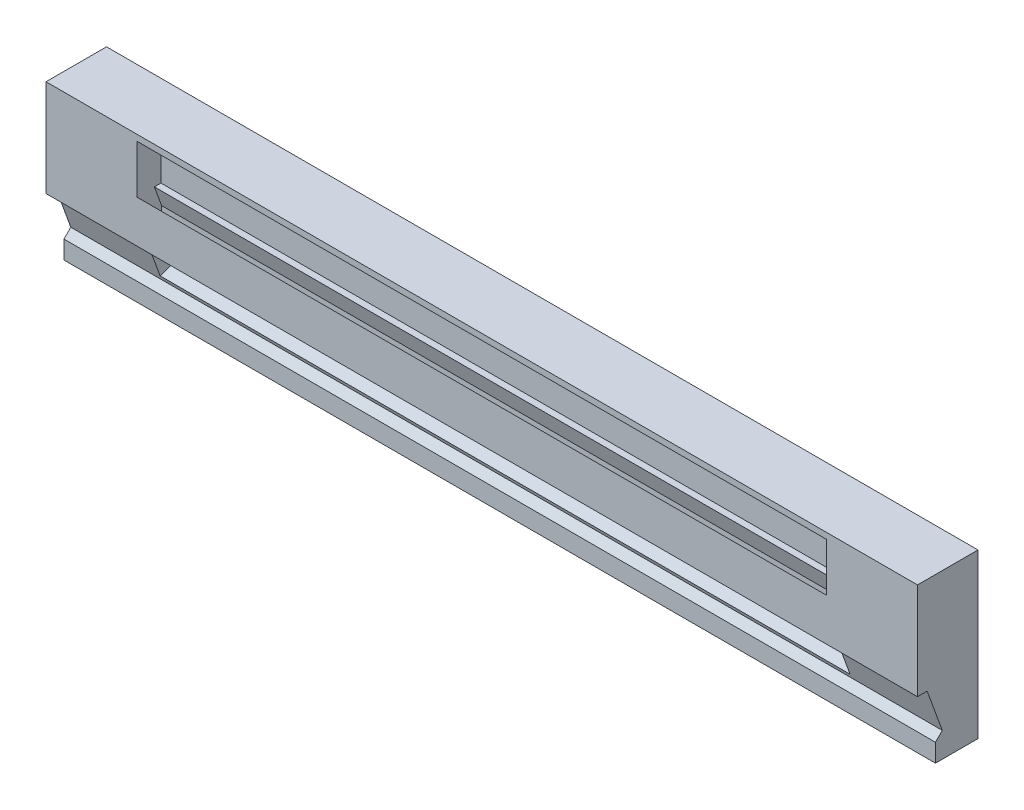
SolidWorks part; units mm, degrees
ref_plane "Front Plane" through (0, 0, 0) normal (0, 0, 1) x (1, 0, 0)
ref_plane "Top Plane" through (0, 0, 0) normal (0, 1, 0) x (1, 0, 0)
ref_plane "Right Plane" through (0, 0, 0) normal (1, 0, 0) x (0, 0, -1)
sketch "Sketch1" plane through (0, 0, 0) normal (1, 0, 0) x (0, 0, -1)
  line L0 (0, 0) -> (44.6494, 0)
  line L1 (44.6494, 0) -> (44.6494, 171.45)
  line L2 (44.6494, 171.45) -> (-18.8506, 171.45)
  line L3 (-18.8506, 171.45) -> (-18.8506, 69.85)
  line L4 (-18.8506, 69.85) -> (-8.6906, 69.85)
  line L5 (-8.6906, 69.85) -> (7.1842, 26.2342)
  line L6 (7.1842, 26.2342) -> (0, 19.05)
  line L7 (0, 19.05) -> (0, 0)
  dimension "D1" = 171.45
  dimension "D2" = 63.5
  dimension "D3" = 101.6
  dimension "D4" = 19.05
  dimension "D5" = 10.16
  dimension "D6" = 10.16
  dimension "D7" = 135
  dimension "D8" = 115
extrude "Boss-Extrude1" add sketch "Sketch1" along normal blind 914.4
sketch "Sketch2" plane through (0, 0, 18.8506) normal (0, 0, 1) x (1, 0, 0)
  line L0 (0, 171.45) -> (0, 69.85) construction
  line L1 (95.25, 165.1) -> (819.15, 165.1)
  line L2 (95.25, 165.1) -> (95.25, 114.3)
  line L3 (95.25, 114.3) -> (819.15, 114.3)
  line L4 (819.15, 165.1) -> (819.15, 114.3)
  line L5 (914.4, 171.45) -> (914.4, 69.85) construction
  line L6 (914.4, 171.45) -> (0, 171.45) construction
  dimension "D1" = 95.25
  dimension "D2" = 95.25
  dimension "D3" = 6.35
  dimension "D4" = 50.8
extrude "Cut-Extrude1" cut sketch "Sketch2" along direction (0, -0.9397, -0.342) on the side against the normal blind 76.2
extrude "Cut-Extrude2" cut sketch "Sketch2<2>" against normal blind 25.4
sketch "Sketch2<2>" plane through (0, 0, 18.8506) normal (0, 0, 1) x (1, 0, 0) same geometry as "Sketch2"
sketch "Sketch3" plane through (0, 5.3778, -14.7753) normal (0, -0.342, 0.9397) x (1, 0, 0)
  line L0 (914.4, 68.6099) -> (0, 68.6099) construction
  line L1 (95.25, 68.6099) -> (819.15, 68.6099)
  line L2 (95.25, 68.6099) -> (95.25, 26.6178)
  line L3 (95.25, 26.6178) -> (819.15, 26.6178)
  line L4 (819.15, 68.6099) -> (819.15, 26.6178)
extrude "Cut-Extrude3" cut sketch "Sketch3" against normal blind 25.4
